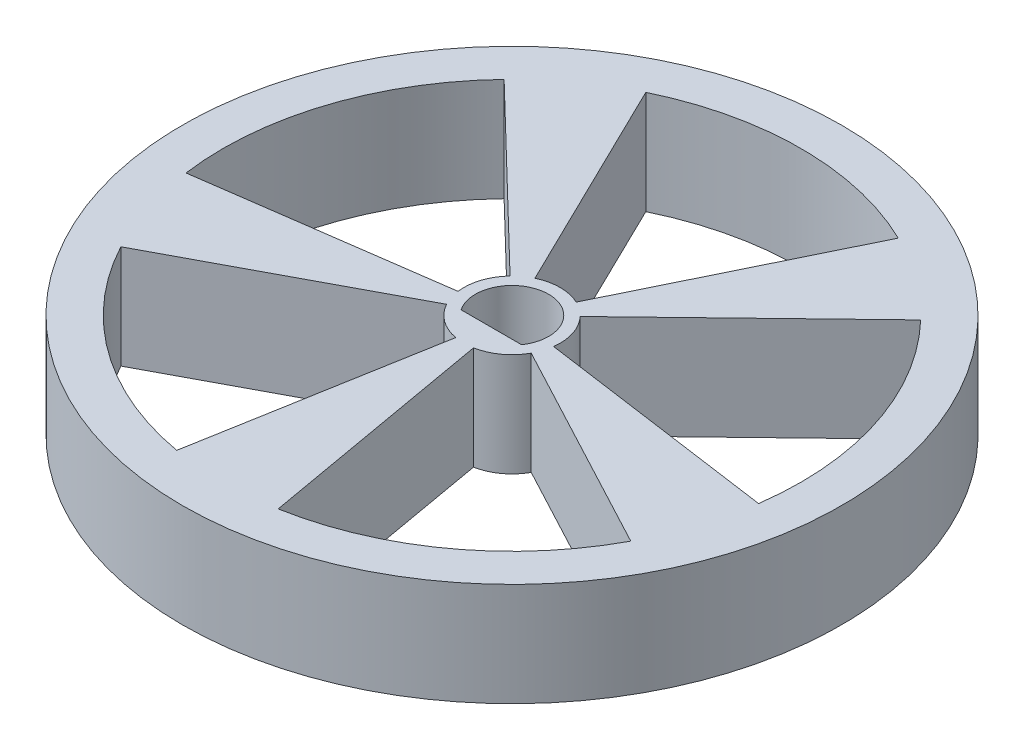
SolidWorks part; units mm, degrees
ref_plane "Front Plane" through (0, 0, 0) normal (0, 0, 1) x (1, 0, 0)
ref_plane "Top Plane" through (0, 0, 0) normal (0, 1, 0) x (1, 0, 0)
ref_plane "Right Plane" through (0, 0, 0) normal (1, 0, 0) x (0, 0, -1)
sketch "Sketch1" plane through (0, 0, 0) normal (0, 1, 0) x (1, 0, 0)
  line L0 (-1.6064, -0.762) -> (1.6064, -0.762)
  line L1 (0, -1.3507) -> (0, -10.6586) construction
  line L2 (-1.8703, -10.4932) -> (-0.254, -1.3266)
  line L3 (1.8703, -10.4932) -> (0.254, -1.3266)
  line L4 (-10.5576, -1.4638) -> (-1.3402, -0.1684)
  line L5 (-9.4017, -5.0213) -> (-1.1832, -0.6515)
  line L6 (-4.6546, 9.5885) -> (-0.5743, 1.2226)
  line L7 (-7.6809, 7.3898) -> (-0.9853, 0.924)
  line L8 (7.6809, 7.3898) -> (0.9853, 0.924)
  line L9 (4.6546, 9.5885) -> (0.5743, 1.2226)
  line L10 (9.4017, -5.0213) -> (1.1832, -0.6515)
  line L11 (10.5576, -1.4638) -> (1.3402, -0.1684)
  circle A0 centre (0, 0) radius 12.1531
  circle A1 centre (0, 0) radius 1.778
  arc A2 (-1.6064, -0.762) -> (1.6064, -0.762) centre (0, 0) cw
  circle A3 centre (0, 0) radius 10.6586
  circle A4 centre (0, 0) radius 1.3507
  point P16 (0, 0)
  point P17 (0, 0)
  point P33 (0, 0)
  dimension "D1" = 3.556
  dimension "D2" = 0.762
  dimension "D3" = 10
  dimension "D4" = 10
  dimension "D5" = 0.254
  dimension "D6" = 0.254
  dimension "D7" = 5
extrude "Boss-Extrude1" add sketch "Sketch1" along normal blind 3.81 contours L6 A3 L7 A1 | L8 A3 L9 A1 | L4 A3 L5 A1 | L10 A3 L11 A1 | L1 A1 L2 A3 | A1 L1 A3 L3 | A0 A3 | A4 L5 L0 | L0 A1 L5 | A4 L0 L5 A1 L2 | L1 A4 L2 A1 | A4 L1 A1 L3 | A4 L3 A1 L10 L0 | A4 L10 L0 A1 L11 | A4 L11 A1 L8 | A4 L4 A1 L0 L5 | A4 L7 A1 L4 | A4 L6 A1 L7 | A4 L9 A1 L6 | A4 L8 A1 L9 | A4 L0 L10 | L10 A1 L0 | A4 L0 region at (-1.4864, 0, 0.4709) region at (-6.865, 0, 2.2306) region at (-1.5196, 0, 0.7921) region at (-1.2305, 0, 0.7253) region at (-0.8869, 0, 1.2461) region at (-1.4492, 0, -0.4709) region at (0, 0, 1.0025) region at (-0.9195, 0, -1.2655) region at (-4.2428, 0, -5.8397) region at (-0.6414, 0, 7.2183) region at (-0.1468, 0, 1.5643) region at (1.2305, 0, 0.7253) region at (0.8869, 0, 1.2461) region at (0, 0, -1.5238) region at (0.6414, 0, 7.2183) region at (0.1468, 0, 1.5643) region at (1.4864, 0, 0.4709) region at (1.5196, 0, 0.7921) region at (0.9195, 0, -1.2655) region at (4.2428, 0, -5.8397) region at (6.865, 0, 2.2306) region at (1.4492, 0, -0.4709) region at (-11.8093, 0, 0)
extrude "Boss-Extrude3" add sketch "Sketch1<8>" along normal blind 0.254 contours A4
sketch "Sketch1<8>" plane through (0, 0, 0) normal (0, 1, 0) x (1, 0, 0) same geometry as "Sketch1"
